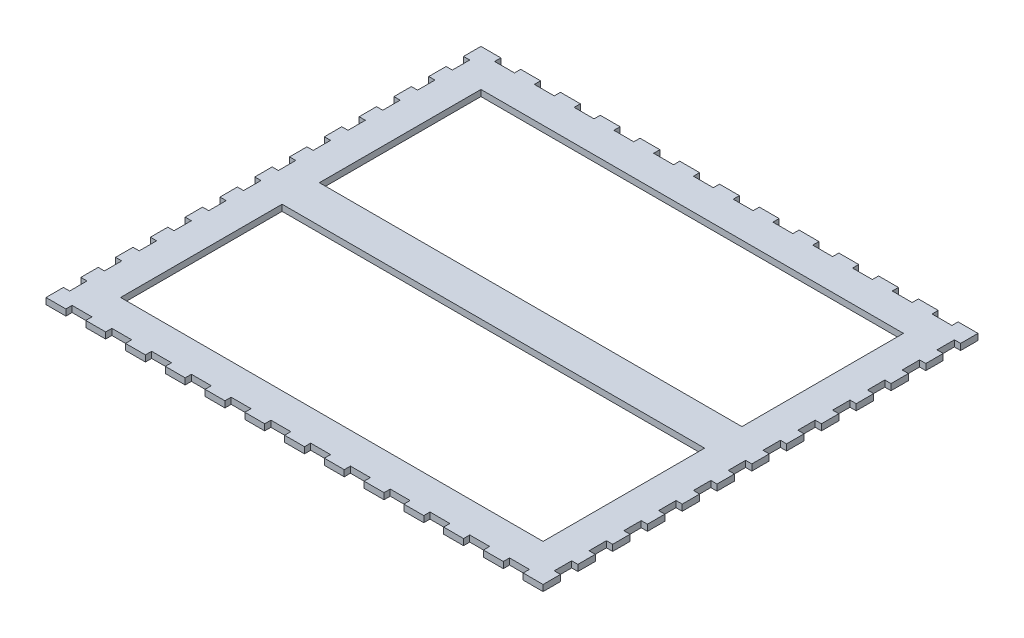
SolidWorks part; units mm, degrees
ref_plane "Plan de face" through (0, 0, 0) normal (0, 0, 1) x (1, 0, 0)
ref_plane "Plan de dessus" through (0, 0, 0) normal (0, 1, 0) x (1, 0, 0)
ref_plane "Plan de droite" through (0, 0, 0) normal (1, 0, 0) x (0, 0, -1)
sketch "Esquisse1" plane through (0, 0, 0) normal (0, 1, 0) x (1, 0, 0)
  line L1 (0, 0) -> (400, 0)
  line L2 (0, 0) -> (0, -350)
  line L3 (0, -350) -> (400, -350)
  line L4 (400, 0) -> (400, -350)
  dimension "D1" = 400
  dimension "D2" = 350
extrude "Boss.-Extru.1" add sketch "Esquisse1" along normal blind 5
ref_plane "Plan2" through (0, 0, 175) normal (0, 0, -1) x (-1, 0, 0)
ref_plane "Plan3" through (200, 0, 0) normal (1, 0, 0) x (0, 0, -1)
sketch "Esquisse2" plane through (0, 5, 0) normal (0, 1, 0) x (1, 0, 0)
  line L0 (400, 0) -> (0, 0) construction
  line L1 (16, 0) -> (32, 0)
  line L2 (16, 0) -> (16, -5)
  line L3 (16, -5) -> (32, -5)
  line L4 (32, 0) -> (32, -5)
  line L7 (0, 0) -> (400, 0) construction
  line L8 (0, 0) -> (0, -350) construction
  dimension "D1" = 400
  dimension "D2" = 16
  dimension "D3" = 16
  dimension "D4" = 5
extrude "Enlèv. mat.-Extru.1" cut sketch "Esquisse2" against normal blind 5
pattern_linear "Répétition linéaire1" count 12 spacing 32 along (1, 0, 0) of "Enlèv. mat.-Extru.1"
sketch "Esquisse3" plane through (0, 5, 0) normal (0, 1, 0) x (1, 0, 0)
  line L0 (0, 0) -> (0, -350) construction
  line L1 (0, -14) -> (5, -14)
  line L2 (0, -14) -> (0, -28)
  line L3 (0, -28) -> (5, -28)
  line L4 (5, -14) -> (5, -28)
  line L5 (0, 0) -> (0, -350) construction
  line L6 (0, -350) -> (400, -350) construction
  line L7 (16, 0) -> (0, 0) construction
  dimension "D4" = 5
  dimension "D1" = 350
  dimension "D2" = 14
  dimension "D3" = 14
extrude "Enlèv. mat.-Extru.2" cut sketch "Esquisse3" against normal blind 5
pattern_linear "Répétition linéaire2" count 12 spacing 28 along (0, 0, 1) of "Enlèv. mat.-Extru.2"
mirror "Symétrie1" about plane through (0, 0, 175) normal (0, 0, -1) of "Répétition linéaire1"
mirror "Symétrie2" about plane through (200, 0, 0) normal (1, 0, 0) of "Répétition linéaire2"
sketch "Esquisse4" plane through (0, 5, 0) normal (0, 1, 0) x (1, 0, 0)
  line L0 (200, -2.75) -> (200, 2.75) construction
  line L1 (30, -30) -> (370, -30)
  line L2 (30, -30) -> (30, -160)
  line L3 (30, -160) -> (370, -160)
  line L4 (370, -30) -> (370, -160)
  line L5 (2.75, -175) -> (-2.75, -175) construction
  dimension "D1" = 340
  dimension "D2" = 170
  dimension "D3" = 130
  dimension "D4" = 15
extrude "Enlèv. mat.-Extru.3" cut sketch "Esquisse4" against normal blind 10
mirror "Symétrie3" about plane through (0, 0, 175) normal (0, 0, -1) of "Enlèv. mat.-Extru.3"
equation "\"D2@Esquisse2\"=\"D1@Esquisse2\"/25"
equation "\"D3@Esquisse2\"=\"D2@Esquisse2\""
equation "\"D4@Répétition linéaire1\"=\"D2@Esquisse2\"*2"
equation "\"D3@Répétition linéaire1\"=\"D2@Esquisse2\"*2"
equation "\"D2@Esquisse3\"=\"D1@Esquisse3\"/25"
equation "\"D3@Esquisse3\"=\"D2@Esquisse3\""
equation "\"D3@Répétition linéaire2\"=\"D2@Esquisse3\"*2"
equation "\"D2@Esquisse4\"=\"D1@Esquisse4\"/2"
